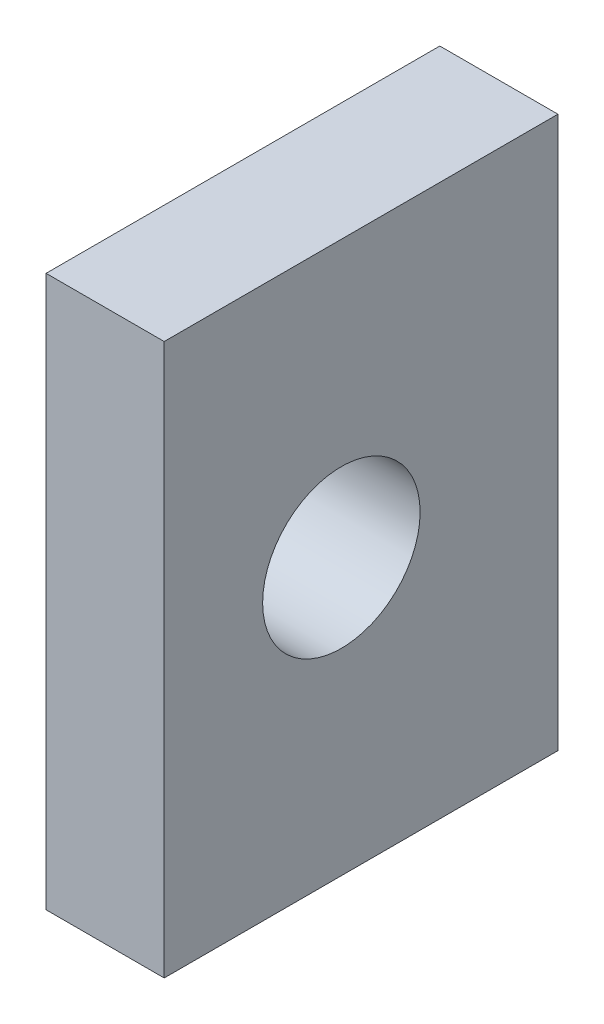
SolidWorks part; units mm, degrees
ref_plane "Front Plane" through (0, 0, 0) normal (0, 0, 1) x (1, 0, 0)
ref_plane "Top Plane" through (0, 0, 0) normal (0, 1, 0) x (1, 0, 0)
ref_plane "Right Plane" through (0, 0, 0) normal (1, 0, 0) x (0, 0, -1)
sketch "Sketch1" plane through (0, 0, 0) normal (1, 0, 0) x (0, 0, -1)
  line L1 (-15.875, -22.225) -> (15.875, -22.225)
  line L2 (-15.875, -22.225) -> (-15.875, 22.225)
  line L3 (-15.875, 22.225) -> (15.875, 22.225)
  line L4 (15.875, -22.225) -> (15.875, 22.225)
  line L5 (-15.875, -22.225) -> (15.875, 22.225) construction
  line L6 (-15.875, 22.225) -> (15.875, -22.225) construction
  circle A0 centre (-1.5875, 0) radius 6.35
  point P0 (0, 0)
  dimension "D3" = 12.7
  dimension "D4" = 14.2875
  dimension "D1" = 44.45
  dimension "D2" = 31.75
extrude "Boss-Extrude1" add sketch "Sketch1" along normal blind 9.525
